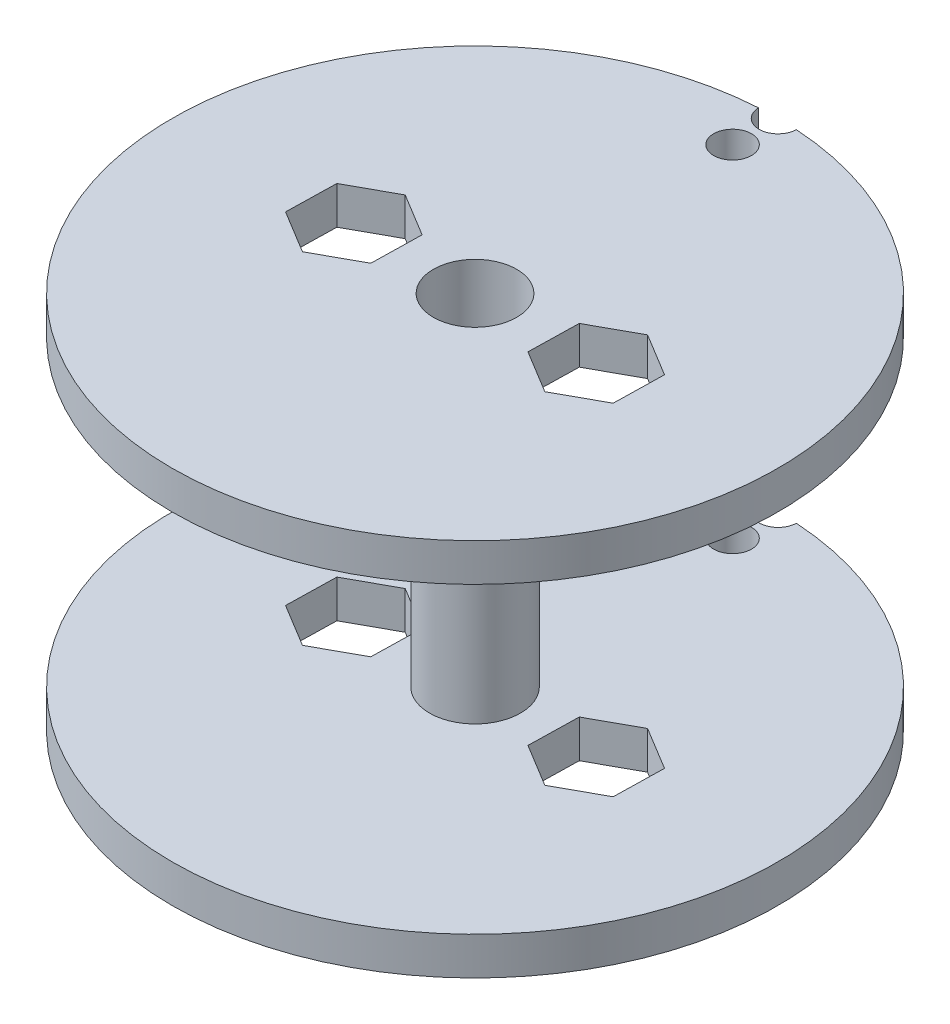
SolidWorks part; units mm, degrees
ref_plane "Front Plane" through (0, 0, 0) normal (0, 0, 1) x (1, 0, 0)
ref_plane "Top Plane" through (0, 0, 0) normal (0, 1, 0) x (1, 0, 0)
ref_plane "Right Plane" through (0, 0, 0) normal (1, 0, 0) x (0, 0, -1)
sketch "Sketch1" plane through (0, 0, 0) normal (0, 1, 0) x (1, 0, 0)
  circle A1 centre (0, 0) radius 20
  circle A2 centre (0, 0) radius 2.75
extrude "Boss-Extrude1" add sketch "Sketch1" along normal blind 2.5
sketch "Sketch2" plane through (0, 2.5, 0) normal (0, 1, 0) x (1, 0, 0)
  circle A0 centre (0, 0) radius 3
  circle A1 centre (0, 0) radius 2.75
sketch "Sketch3" plane through (0, 0, 0) normal (0, -1, 0) x (1, 0, 0)
  line L0 (-5.1613, 1.7213) -> (-8.0713, 3.319)
  line L1 (5.1613, -1.7213) -> (8.0713, -3.319)
  line L2 (8.0713, -3.319) -> (10.91, -1.5977)
  line L3 (10.91, -1.5977) -> (10.8387, 1.7213)
  line L4 (10.8387, 1.7213) -> (7.9287, 3.319)
  line L5 (7.9287, 3.319) -> (5.09, 1.5977)
  line L6 (5.09, 1.5977) -> (5.1613, -1.7213)
  line L7 (-8.0713, 3.319) -> (-10.91, 1.5977)
  line L8 (-10.91, 1.5977) -> (-10.8387, -1.7213)
  line L9 (-10.8387, -1.7213) -> (-7.9287, -3.319)
  line L10 (-7.9287, -3.319) -> (-5.09, -1.5977)
  line L11 (-5.09, -1.5977) -> (-5.1613, 1.7213)
  circle A0 centre (8, 0) radius 2.875 construction
  point P17 (0, 0)
  dimension "D2" = 8
  dimension "D1" = 2
extrude "Cut-Extrude3" cut sketch "Sketch3" against normal blind 2.5
sketch "Sketch4" plane through (0, 2.5, 0) normal (0, 1, 0) x (1, 0, 0)
  circle A0 centre (0, 17) radius 1.25
  circle A1 centre (0, 20) radius 1.25
  circle A2 centre (0, 0) radius 20 construction
  dimension "D1" = 17
extrude "Cut-Extrude4" cut sketch "Sketch4" against normal blind 5
sketch "Sketch5" plane through (0, 2.5, 0) normal (0, 1, 0) x (1, 0, 0)
  circle A0 centre (0, -16.2068) radius 3.1
extrude "Cut-Extrude5" [suppressed] cut sketch "Sketch5" along normal blind 2.5 from surface
extrude "Boss-Extrude2" add sketch "Sketch2" along normal blind 10
mirror "Mirror7" about plane through (0, 12.5, 0) normal (0, 1, 0) of bodies 107
